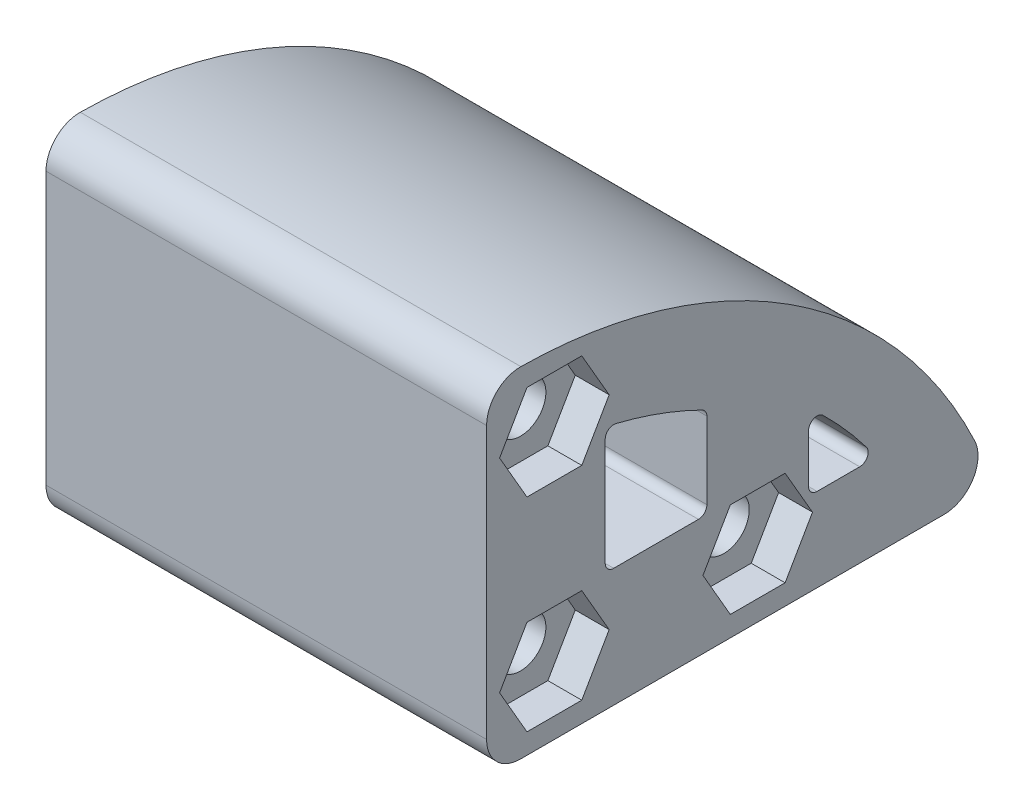
SolidWorks part; units mm, degrees
ref_plane "Front Plane" through (0, 0, 0) normal (0, 0, 1) x (1, 0, 0)
ref_plane "Top Plane" through (0, 0, 0) normal (0, 1, 0) x (1, 0, 0)
ref_plane "Right Plane" through (0, 0, 0) normal (1, 0, 0) x (0, 0, -1)
sketch "Sketch1" plane through (0, 0, 0) normal (1, 0, 0) x (0, 0, -1)
  line L0 (-4, 14.0452) -> (-4, -2)
  line L1 (-2, -4) -> (23, -4)
  line L3 (0, 0) -> (0, 12) construction
  line L4 (0, 12) -> (12, 0) construction
  line L5 (12, 0) -> (0, 0) construction
  line L9 (3, 9.8456) -> (3, 3.5)
  line L10 (3.5, 3) -> (8.5, 3)
  line L11 (9, 3.5) -> (9, 8.0281)
  line L12 (12, 1.5) -> (12, 10.4567) construction
  line L13 (15, 4.2866) -> (15, 1.4278)
  line L14 (15.5, 0.9278) -> (18.0187, 0.9278)
  circle A0 centre (0, 0) radius 1.5
  circle A1 centre (0, 12) radius 1.5
  circle A2 centre (12, 0) radius 1.5
  arc A4 (-1.9771, 16.0451) -> (24.8086, -1.1462) centre (-2.3205, -13.953) cw
  arc A5 (23, -4) -> (24.8086, -1.1462) centre (23, -2) ccw
  arc A6 (-4, -2) -> (-2, -4) centre (-2, -2) ccw
  arc A7 (-1.9771, 16.0451) -> (-4, 14.0452) centre (-2, 14.0452) ccw
  arc A8 (3.6188, 10.3313) -> (8.7208, 8.4767) centre (-2.3205, -13.953) cw
  arc A9 (15.8494, 4.6442) -> (18.4175, 1.7294) centre (-2.3205, -13.953) cw
  arc A10 (15.8494, 4.6442) -> (15, 4.2866) centre (15.5, 4.2866) ccw
  arc A11 (18.0187, 0.9278) -> (18.4175, 1.7294) centre (18.0187, 1.4278) ccw
  arc A12 (15, 1.4278) -> (15.5, 0.9278) centre (15.5, 1.4278) ccw
  arc A13 (3, 3.5) -> (3.5, 3) centre (3.5, 3.5) ccw
  arc A14 (8.5, 3) -> (9, 3.5) centre (8.5, 3.5) ccw
  arc A15 (8.7208, 8.4767) -> (9, 8.0281) centre (8.5, 8.0281) cw
  arc A16 (3.6188, 10.3313) -> (3, 9.8456) centre (3.5, 9.8456) ccw
  point P30 (-4, -4)
  point P33 (-4, 16)
  point P37 (19, 0.9278)
  point P40 (15, 0.9278)
  dimension "D1" = 3
  dimension "D6" = 30
  dimension "D8" = 2
  dimension "D11" = 5
  dimension "D13" = 4
  dimension "D16" = 0.5
  dimension "D2" = 12
  dimension "D3" = 12
  dimension "D4" = 4
  dimension "D5" = 4
  dimension "D7" = 20
  dimension "D9" = 3
  dimension "D10" = 3
  dimension "D12" = 3
  dimension "D14" = 3
  dimension "D15" = 4
  dimension "D17" = 25
extrude "Boss-Extrude1" add sketch "Sketch1" along normal blind 26
sketch "Sketch2" plane through (0, 0, 0) normal (1, 0, 0) x (0, 0, -1)
  line L1 (-1.6166, 9.2) -> (1.6166, 9.2)
  line L2 (1.6166, 9.2) -> (3.2332, 12)
  line L3 (3.2332, 12) -> (1.6166, 14.8)
  line L4 (1.6166, 14.8) -> (-1.6166, 14.8)
  line L5 (-1.6166, 14.8) -> (-3.2332, 12)
  line L6 (-3.2332, 12) -> (-1.6166, 9.2)
  line L7 (1.6166, 2.8) -> (-1.6166, 2.8)
  line L8 (-1.6166, 2.8) -> (-3.2332, 0)
  line L9 (-3.2332, 0) -> (-1.6166, -2.8)
  line L10 (-1.6166, -2.8) -> (1.6166, -2.8)
  line L11 (1.6166, -2.8) -> (3.2332, 0)
  line L12 (3.2332, 0) -> (1.6166, 2.8)
  line L13 (15.2332, 0) -> (13.6166, 2.8)
  line L14 (13.6166, 2.8) -> (10.3834, 2.8)
  line L15 (10.3834, 2.8) -> (8.7668, 0)
  line L16 (8.7668, 0) -> (10.3834, -2.8)
  line L17 (10.3834, -2.8) -> (13.6166, -2.8)
  line L18 (13.6166, -2.8) -> (15.2332, 0)
  circle A0 centre (0, 12) radius 2.8 construction
  circle A1 centre (0, 0) radius 2.8 construction
  circle A2 centre (12, 0) radius 2.8 construction
  dimension "D1" = 5.6
  dimension "D2" = 5.6
  dimension "D3" = 5.6
extrude "Cut-Extrude1" cut sketch "Sketch2" along normal blind 2
extrude "Cut-Extrude2" cut sketch "Sketch2<3>" against normal blind 2 from surface starting at face at (26, 12, -1.5)
sketch "Sketch2<3>" plane through (0, 0, 0) normal (1, 0, 0) x (0, 0, -1) same geometry as "Sketch2"
